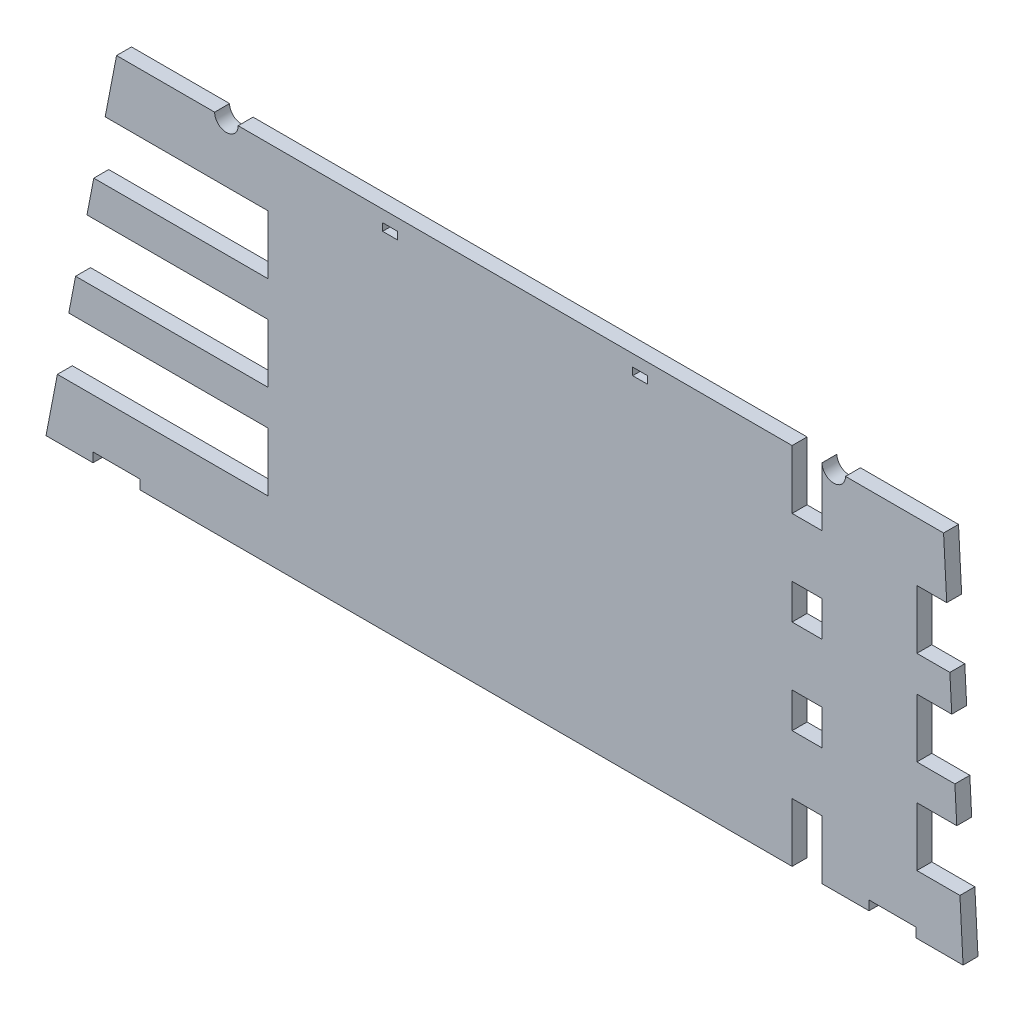
SolidWorks part; units mm, degrees
ref_plane "Front Plane" through (0, 0, 0) normal (0, 0, 1) x (1, 0, 0)
ref_plane "Top Plane" through (0, 0, 0) normal (0, 1, 0) x (1, 0, 0)
ref_plane "Right Plane" through (0, 0, 0) normal (1, 0, 0) x (0, 0, -1)
sketch "Sketch1" plane through (0, 0, 0) normal (0, 0, 1) x (1, 0, 0)
  line L0 (-159.5062, 0) -> (117.7937, 0)
  line L1 (190.4938, 0) -> (189.1571, 25)
  line L2 (182.2063, 155) -> (140.4938, 155)
  line L3 (-169.5062, 155) -> (-174.345, 130)
  line L4 (-199.5062, 0) -> (-179.5062, 0)
  line L5 (-179.5062, 0) -> (-179.5062, 4)
  line L6 (-179.5062, 4) -> (-159.5062, 4)
  line L7 (-159.5062, 4) -> (-159.5062, 0)
  line L8 (-169.5062, 155) -> (-127.7938, 155)
  line L9 (150.4938, 0) -> (150.4938, 4)
  line L10 (150.4938, 4) -> (170.4938, 4)
  line L11 (170.4938, 4) -> (170.4938, 0)
  line L12 (170.4938, 0) -> (190.4938, 0)
  line L13 (-169.5062, 155) -> (-127.7938, 155)
  line L14 (0, 155) -> (0, 0) construction
  line L15 (-117.7938, 155) -> (117.7937, 155)
  line L16 (-174.345, 130) -> (-105.0938, 130)
  line L17 (-105.0938, 130) -> (-105.0937, 105)
  line L18 (-105.0937, 105) -> (-179.1837, 105)
  line L19 (-182.0869, 90) -> (-105.0937, 90)
  line L20 (-105.0937, 90) -> (-105.0937, 65)
  line L21 (-105.0937, 65) -> (-186.9256, 65)
  line L22 (-189.8288, 50) -> (-105.0938, 50)
  line L23 (-105.0938, 50) -> (-105.0938, 25)
  line L24 (-105.0938, 25) -> (-194.6675, 25)
  line L25 (-179.1837, 105) -> (-182.0869, 90)
  line L26 (-186.9256, 65) -> (-189.8288, 50)
  line L27 (-194.6675, 25) -> (-199.5062, 0)
  line L28 (117.7937, 90) -> (117.7937, 105)
  line L29 (117.7937, 105) -> (130.4938, 105)
  line L30 (130.4938, 105) -> (130.4938, 90)
  line L31 (130.4938, 90) -> (117.7937, 90)
  line L32 (-105.0937, 105) -> (-105.0937, 90) construction
  line L33 (117.7937, 50) -> (117.7937, 65)
  line L34 (117.7937, 65) -> (130.4938, 65)
  line L35 (130.4938, 65) -> (130.4938, 50)
  line L36 (130.4938, 50) -> (117.7937, 50)
  line L37 (130.4938, 0) -> (130.4938, 25)
  line L38 (130.4938, 25) -> (117.7937, 25)
  line L39 (117.7937, 25) -> (117.7937, 0)
  line L40 (117.7937, 155) -> (117.7938, 130)
  line L41 (117.7938, 130) -> (130.4938, 130)
  line L42 (130.4938, 130) -> (130.4938, 155)
  line L43 (130.4938, 0) -> (150.4938, 0)
  line L44 (183.5429, 130) -> (170.8429, 130)
  line L45 (170.8429, 130) -> (170.8429, 105)
  line L46 (170.8429, 105) -> (184.8796, 105)
  line L47 (185.6817, 90) -> (170.8429, 90)
  line L48 (170.8429, 90) -> (170.8429, 65)
  line L49 (170.8429, 65) -> (187.0183, 65)
  line L50 (187.8204, 50) -> (170.8429, 50)
  line L51 (170.8429, 50) -> (170.8429, 25)
  line L52 (170.8429, 25) -> (189.1571, 25)
  line L53 (183.5429, 130) -> (182.2063, 155)
  line L54 (185.6817, 90) -> (184.8796, 105)
  line L55 (187.8204, 50) -> (187.0183, 65)
  line L56 (-56.35, 150) -> (-56.35, 146.825)
  line L57 (-56.35, 146.825) -> (-50, 146.825)
  line L58 (-50, 146.825) -> (-50, 150)
  line L59 (-50, 150) -> (-56.35, 150)
  line L60 (50, 150) -> (56.35, 150)
  line L61 (50, 146.825) -> (50, 150)
  line L62 (56.35, 146.825) -> (50, 146.825)
  line L63 (56.35, 150) -> (56.35, 146.825)
  arc A0 (-127.7938, 155) -> (-117.7938, 155) centre (-122.7938, 155) ccw
  arc A1 (140.4938, 155) -> (130.4938, 155) centre (135.4938, 155) cw
  dimension "D18" = 6.35
  dimension "D2" = 20
  dimension "D3" = 20
  dimension "D4" = 268.2875
  dimension "D5" = 15
  dimension "D6" = 10
  dimension "D7" = 12.7
  dimension "D8" = 4
  dimension "D9" = 10
  dimension "D10" = 310
  dimension "D11" = 5
  dimension "D12" = 25
  dimension "D13" = 12.7
  dimension "D14" = 25
  dimension "D15" = 12.7
  dimension "D16" = 155
  dimension "D17" = 50
  dimension "D19" = 5
  dimension "D20" = 3.175
extrude "Extrude1" add sketch "Sketch1" along normal blind 6.35 contours L0 L15 A0 L8 L3 L4 L5 L6 L7 | L0 L9 L10 L11 L12 L1 L2 A1 L15 region at (11.7768, 76.4275, 0)
